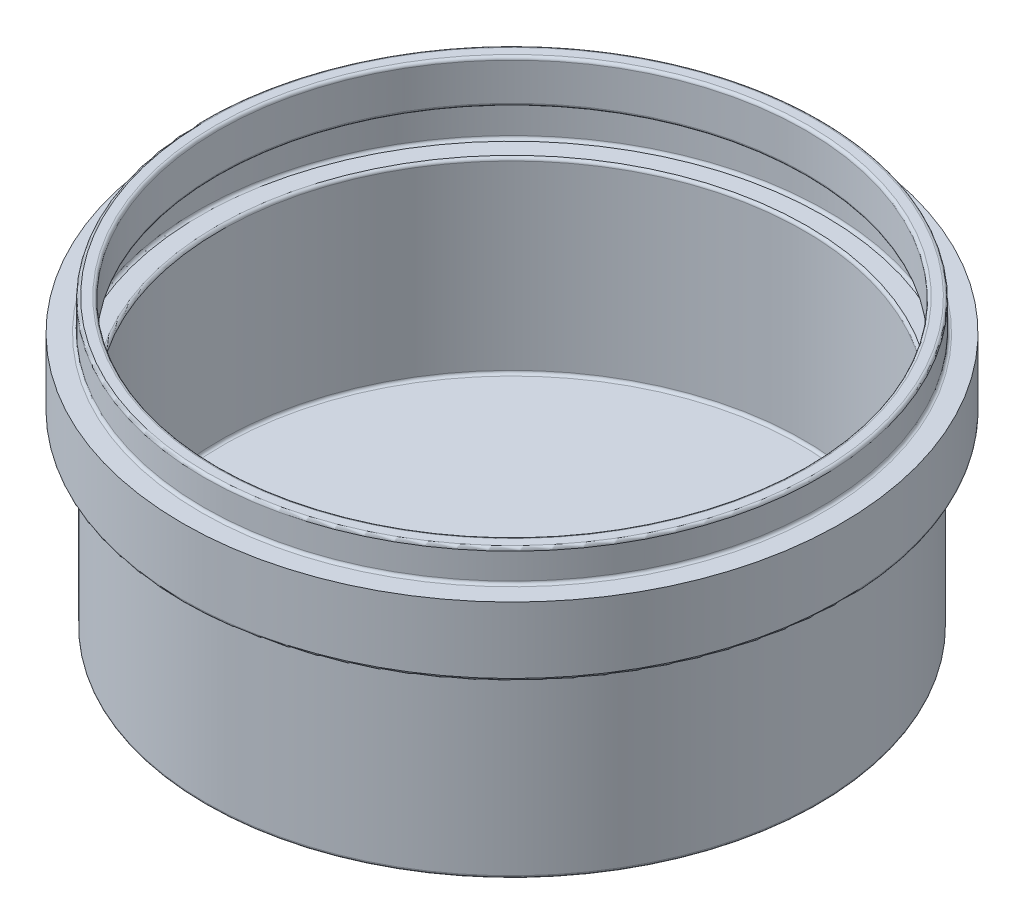
SolidWorks part; units mm, degrees
ref_plane "Plano frontal" through (0, 0, 0) normal (0, 0, 1) x (1, 0, 0)
ref_plane "Plano superior" through (0, 0, 0) normal (0, 1, 0) x (1, 0, 0)
ref_plane "Plano direito" through (0, 0, 0) normal (1, 0, 0) x (0, 0, -1)
sketch "Esboço1" plane through (0, 0, 0) normal (0, 1, 0) x (1, 0, 0)
  circle A0 centre (0, 0) radius 53.25
  dimension "D1" = 106.5
extrude "Ressalto-extrusão1" add sketch "Esboço1" along normal blind 2.5
sketch "Esboço2" plane through (0, 2.5, 0) normal (0, 1, 0) x (1, 0, 0)
  circle A0 centre (0, 0) radius 53.25
  circle A1 centre (0, 0) radius 50.75
  circle A2 centre (0, 0) radius 53.25 construction
  dimension "D1" = 2.5
extrude "Ressalto-extrusão2" add sketch "Esboço2" along normal blind 30
sketch "Esboço3" plane through (0, 32.5, 0) normal (0, 1, 0) x (1, 0, 0)
  circle A0 centre (0, 0) radius 57.25
  circle A3 centre (0, 0) radius 53.25 construction
  dimension "D1" = 4
extrude "Ressalto-extrusão3" add sketch "Esboço3" along normal blind 12 separate body
sketch "Esboço6" plane through (0, 44.5, 0) normal (0, 1, 0) x (1, 0, 0)
  circle A0 centre (0, 0) radius 53.5
  dimension "D1" = 107
extrude "Ressalto-extrusão4" add sketch "Esboço6" along normal blind 5.5
sketch "Esboço7" plane through (0, 50, 0) normal (0, 1, 0) x (1, 0, 0)
  circle A0 centre (0, 0) radius 51
  circle A2 centre (0, 0) radius 53.5 construction
  dimension "D1" = 2.5
extrude "Corte-extrusão4" cut sketch "Esboço7" against normal blind 7.5
sketch "Esboço8" plane through (0, 42.5, 0) normal (0, 1, 0) x (1, 0, 0)
  circle A0 centre (0, 0) radius 54.75
  circle A1 centre (0, 0) radius 57.25 construction
  dimension "D1" = 2.5
extrude "Corte-extrusão5" cut sketch "Esboço8" against normal blind 7.5
sketch "Esboço9" plane through (0, 35, 0) normal (0, 1, 0) x (1, 0, 0)
  circle A0 centre (0, 0) radius 50.75
  circle A1 centre (0, 0) radius 53.25 construction
  dimension "D1" = 2.5
extrude "Corte-extrusão6" cut sketch "Esboço9" against normal blind 7.5
combine bodies "Combinar3" operation type add bodies to combine 111 102
fillet "Filete1" radius 0.5 6 edges at (0, 32.5, 57.25) (0, 50, 51) (0, 50, 53.5) (0, 44.5, 53.5) (0, 32.5, 53.25) (0, 0, 53.25)
fillet "Filete2" radius 0.5 5 edges at (0, 42.5, 51) (0, 35, 54.75) (0, 2.5, 50.75) (0, 35, 50.75) (0, 42.5, 54.75)
